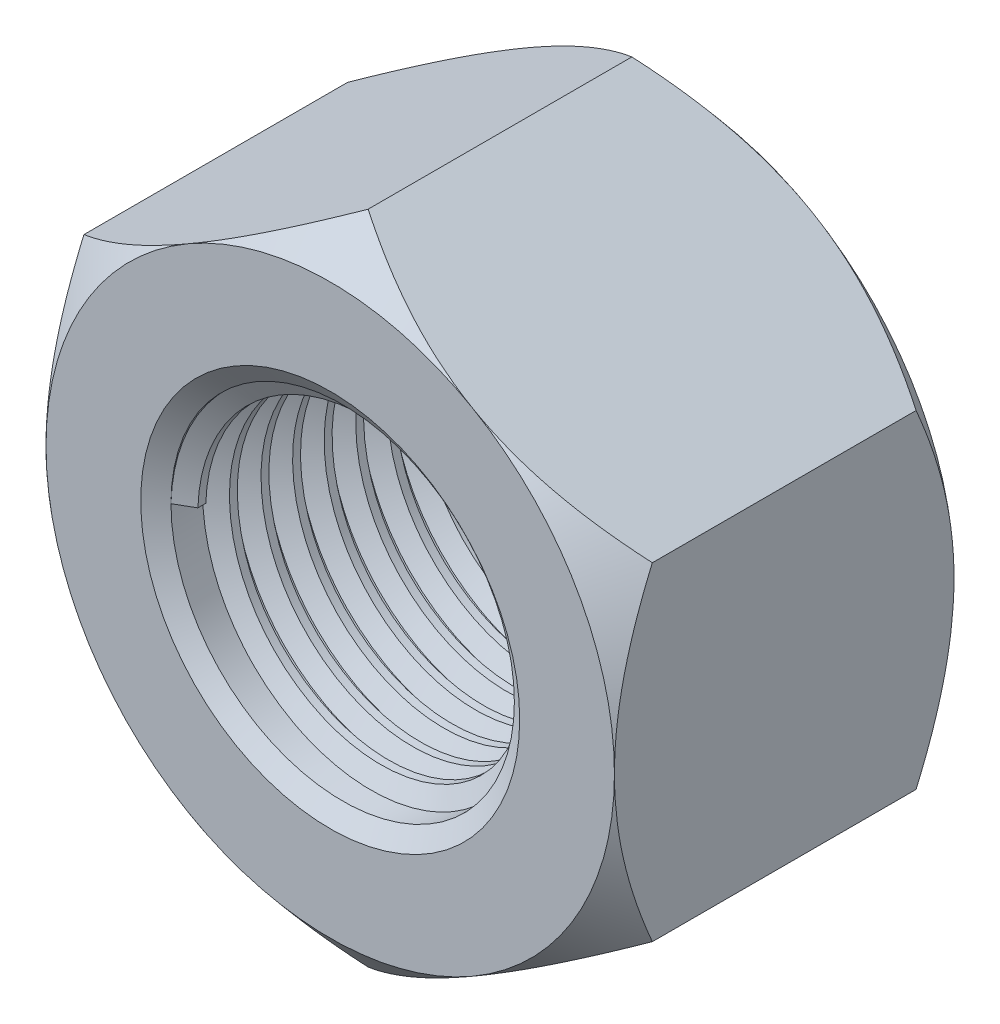
SolidWorks part; units mm, degrees
extrude "BaseNut" add sketch "BaseNutSke" against normal blind 11.3792
sketch "BaseNutSke" plane through (0, 0, 0) normal (0, 0, 1) x (1, 0, 0)
  line L6 (9.525, 5.4993) -> (9.525, -5.4993)
  line L7 (-9.525, 5.4993) -> (-9.525, -5.4993)
  line L8 (9.525, 5.4993) -> (0, 10.9985)
  line L9 (0, 10.9985) -> (-9.525, 5.4993)
  line L10 (-9.525, -5.4993) -> (0, -10.9985)
  line L11 (0, -10.9985) -> (9.525, -5.4993)
  circle A0 centre (0, 0) radius 5.7544
  dimension "D2" = 9.525
  dimension "D3" = 9.525
  dimension "D1" = 120
  dimension "D4" = 9.525
cosmetic thread "ThreadCosmetic" [suppressed] parameters "Thread_major"=12.7
pattern_linear "ThdSchPat" [suppressed]
revolve "ThreadSchematic" [suppressed] cut sketch "ThdSchSke" angle 360 about L6
sketch "ThdSchSke" plane through (0, 0, 0) normal (0, 1, 0) x (1, 0, 0)
  line L0 (-6.35, 0.0254) -> (-5.7544, 0.4425)
  line L1 (-5.7544, 0.4425) -> (-2.8772, 0.4425)
  line L2 (-2.8772, 0.4425) -> (-2.8772, -0.3917)
  line L3 (-2.8772, -0.3917) -> (-5.7544, -0.3917)
  line L4 (-5.7544, -0.3917) -> (-6.35, 0.0254)
  line L5 (-3.175, 1.27) -> (3.175, 1.27) construction
  line L6 (0, 1.27) -> (0, -2.9874) construction
  line L7 (0, 10.9367) -> (0, 0.4171) construction
  dimension "SideAngle" = 55
  dimension "Advance" = 1.27
  dimension "D1" = 0.0254
ref_plane "Plane1" through (0, 0, 0) normal (0, 0, 1) x (1, 0, 0)
ref_plane "Plane2" through (0, 0, 0) normal (0, 1, 0) x (1, 0, 0)
ref_plane "Plane3" through (0, 0, 0) normal (1, 0, 0) x (0, 0, -1)
sketch "Sketch4" plane through (0, 0, 0) normal (1, 0, 0) x (0, 0, -1)
  line L0 (11.3792, 9.525) -> (10.9728, 9.525)
  line L1 (11.3792, 9.525) -> (11.3792, 23.6985)
  line L2 (10.9728, 23.6985) -> (11.3792, 23.6985)
  line L3 (10.9728, 23.6985) -> (10.9728, 9.525)
  line L4 (0, 0) -> (34.925, 0) construction
  line L6 (11.3792, 5.4993) -> (11.3792, 10.9985) construction
  line L7 (0, 9.525) -> (-12.7, 9.525)
  line L8 (0, 5.4993) -> (0, 10.9985) construction
  line L9 (1.27, 10.9985) -> (1.27, 23.6985)
  line L10 (1.27, 23.6985) -> (-12.7, 23.6985)
  line L11 (-12.7, 23.6985) -> (-12.7, 9.525)
  line L12 (0, 9.525) -> (1.27, 10.9985)
  line L14 (0, 5.4993) -> (0, -5.4993) construction
  line L15 (11.3792, 10.9985) -> (0, 10.9985) construction
  dimension "D1" = 9.525
  dimension "D2" = 1.27
  dimension "D3" = 12.7
  dimension "D4" = 12.7
revolve "Bearing-Face" [suppressed] cut sketch "Sketch4" angle 360 about L4
sketch "Sketch3" plane through (0, 0, 0) normal (1, 0, 0) x (0, 0, -1)
  line L0 (11.3792, 9.525) -> (10.1092, 10.9985)
  line L1 (10.1092, 10.9985) -> (10.1092, 23.6985)
  line L2 (10.1092, 23.6985) -> (24.0792, 23.6985)
  line L3 (24.0792, 23.6985) -> (24.0792, 9.525)
  line L4 (24.0792, 9.525) -> (11.3792, 9.525)
  line L5 (11.3792, 5.4993) -> (11.3792, 10.9985) construction
  line L6 (11.3792, 10.9985) -> (0, 10.9985) construction
  line L7 (0, 0) -> (38.6776, 0) construction
  line L8 (11.3792, 0) -> (0, 0) construction
  line L9 (5.6896, 10.9985) -> (5.6896, 44.222) construction
  line L10 (1.27, 23.6985) -> (-12.7, 23.6985)
  line L11 (-12.7, 23.6985) -> (-12.7, 9.525)
  line L12 (-12.7, 9.525) -> (0, 9.525)
  line L13 (0, 9.525) -> (1.27, 10.9985)
  line L14 (1.27, 10.9985) -> (1.27, 23.6985)
  line L16 (11.3792, 10.9985) -> (0, 10.9985) construction
  dimension "D1" = 9.525
  dimension "D2" = 1.27
  dimension "D4" = 12.7
  dimension "D3" = 12.7
revolve "Double-Chamfer" cut sketch "Sketch3" angle 360 about L7
sketch "Sketch5" plane through (0, 0, 0) normal (1, 0, 0) x (0, 0, -1)
  line L0 (11.3538, 6.35) -> (10.895, 5.6948)
  line L1 (11.4046, 6.35) -> (11.3538, 6.35)
  line L2 (11.4046, 6.35) -> (11.4046, 5.6948)
  line L3 (11.4046, 5.6948) -> (10.895, 5.6948)
  line L6 (-0.0508, 6.35) -> (0, 6.35)
  line L7 (0, 6.35) -> (0.4588, 5.6948)
  line L9 (0.4588, 5.6948) -> (-0.0508, 5.6948)
  line L10 (-0.0508, 5.6948) -> (-0.0508, 6.35)
  line L11 (25.0375, 0) -> (38.388, 0) construction
  line L12 (11.3792, 0) -> (0, 0) construction
  dimension "D1" = 35
  dimension "D2" = 0.0508
  dimension "ThreadMajor" = 6.35
  dimension "Offset1" = 11.4046
revolve "EndChamfer" cut sketch "Sketch5" angle 360 about L11
thread "Thread1" pitch 1.0583 method extrude profile "Thread Profile1" start angle 0, offset 0, length 9.652, pitch 1.0583, diameter 11.5087
ref_plane "Plane4" through (-5.7544, 0, -0.4171) normal (0, -1, 0) x (-1, 0, 0)
sketch "Thread Profile1" plane through (-5.7544, 0, -0.4171) normal (0, -1, 0) x (-1, 0, 0)
  line L0 (0, 0) -> (0, 1.0583) construction
  line L11 (0, 0) -> (0, 0.926)
  line L12 (0, 0.926) -> (-0.5728, 0.5953)
  line L13 (-0.5728, 0.5953) -> (-0.5728, 0.3307)
  line L15 (-0.5728, 0.3307) -> (0, 0)
  line L17 (-0.5728, 0.463) -> (0, 0.463) construction
  point P2 (0, 0)
  dimension "Pitch" = 1.0583
  dimension "Profile_Angle" = 60
  dimension "Profile_Land" = 0.2646
  dimension "Profile_Height" = 0.5728
equation "\"D2@BaseNutSke\" = \"Width_flats@BaseNutSke\" / 2"
equation "\"D3@BaseNutSke\" = \"Width_flats@BaseNutSke\" / 2"
equation "\"D1@Sketch3\" = \"Width_flats@BaseNutSke\" /2"
equation "\"D2@Sketch3\" = \"Thread_major@ThreadCosmetic\" *.1"
equation "\"D1@Sketch4\" = \"D2@BaseNutSke\""
equation "\"D2@Sketch4\" = \"Thread_major@ThreadCosmetic\" *.10"
equation "\"D4@BaseNutSke\" = \"D3@BaseNutSke\""
equation "\"Thread_major@ThdSchSke\" = \"Thread_major@ThreadCosmetic\""
equation "\"Tap_Drill@ThdSchSke\" = \"Tap_drill@BaseNutSke\""
equation "\"OverCut@ThdSchSke\" = \"Tap_Drill@ThdSchSke\" * 0.5"
equation "\"Num_threads@ThdSchPat\" = int(  ( \"Thickness@BaseNut\" - 0.002 ) / \"Advance@ThdSchSke\" + 0.999 )  + 1"
equation "\"Advance@ThdSchPat\" = ( \"Thickness@BaseNut\" - 0.002 ) /  (\"Num_threads@ThdSchPat\" - 1) 'relax it"
equation "' \"Num_threads@ThdSchPat\" = \"Num_threads@ThdSchPat\" - sgn( \"Num_threads@ThdSchPat\" - 1) '---chamfered tips only---"
equation "\"ThreadMajor@Sketch5\" = \"Thread_major@ThreadCosmetic\" * 0.5"
equation "\"ChamferDepth@Sketch5\" = (\"Thread_major@ThreadCosmetic\" - \"Tap_drill@BaseNutSke\") * 0.55"
equation "\"Offset1@Sketch5\" = \"Thickness@BaseNut\" + 0.001"
equation "\"Offset2@Sketch5\" = \"Offset1@Sketch5\" + 0.002"
